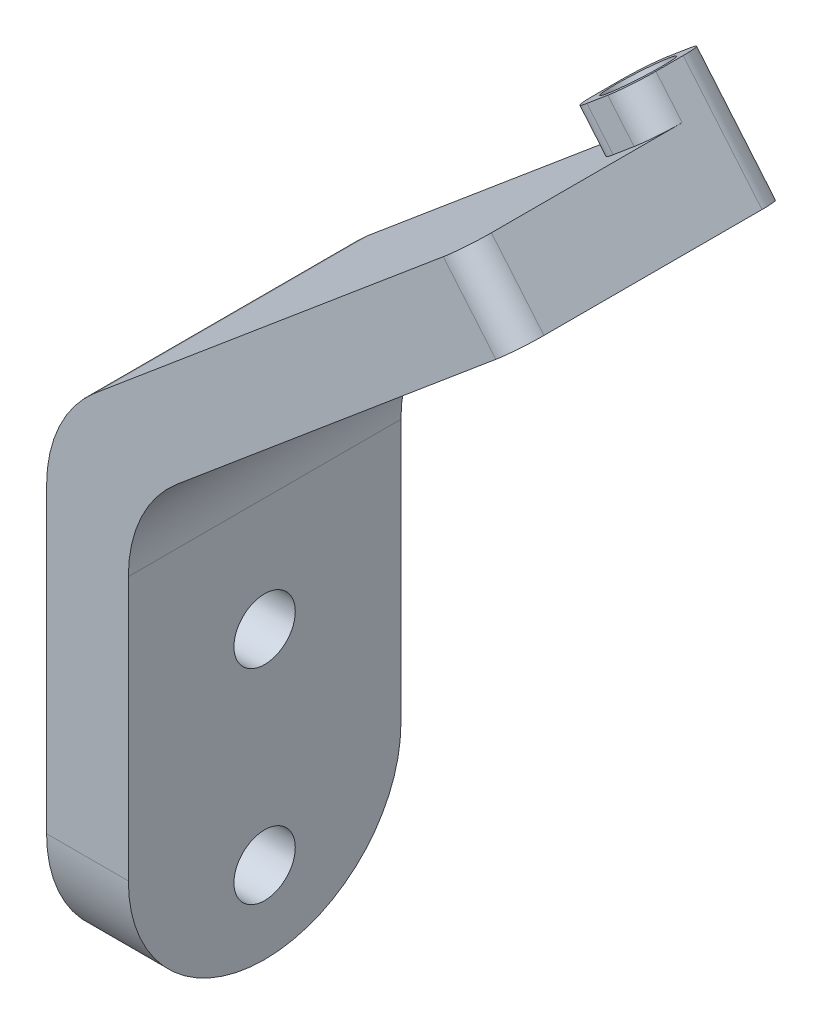
SolidWorks part; units mm, degrees
ref_plane "Plan de face" through (0, 0, 0) normal (0, 0, 1) x (1, 0, 0)
ref_plane "Plan de dessus" through (0, 0, 0) normal (0, 1, 0) x (1, 0, 0)
ref_plane "Plan de droite" through (0, 0, 0) normal (1, 0, 0) x (0, 0, -1)
sketch "Esquisse1" plane through (0, 0, 0) normal (0, 0, 1) x (1, 0, 0)
  line L0 (0, 0) -> (0, 36.7978)
  line L1 (0, 36.7978) -> (30.6418, 62.5094)
  line L2 (30.6418, 62.5094) -> (34.4985, 57.9131)
  line L3 (34.4985, 57.9131) -> (6, 34)
  line L4 (6, 34) -> (6, 0)
  line L5 (6, 0) -> (0, 0)
  dimension "D1" = 34
  dimension "D2" = 130
  dimension "D3" = 40
  dimension "D4" = 6
  dimension "D5" = 6
extrude "Boss.-Extru.1" add sketch "Esquisse1" along normal blind 20
sketch "Esquisse2" plane through (6, 0, 0) normal (1, 0, 0) x (0, 0, -1)
  line L0 (-10, 0) -> (-10, 34) construction
  line L1 (-20, 0) -> (0, 0) construction
  line L2 (-20, 34) -> (0, 34) construction
  circle A0 centre (-10, 6) radius 2.25
  circle A1 centre (-10, 21) radius 2.25
  dimension "D1" = 6
  dimension "D2" = 15
  dimension "D3" = 4.5
extrude "Enlèv. mat.-Extru.1" cut sketch "Esquisse2" against normal through all both and the other way through all
sketch "Esquisse3" plane through (-18.1194, 21.5939, 0) normal (-0.6428, 0.766, 0) x (0.766, 0.6428, 0)
  line L0 (63.6532, 0) -> (23.6532, 0) construction
  line L1 (63.6532, -6) -> (57.6532, -6)
  line L2 (63.6532, -6) -> (63.6532, 0)
  line L3 (63.6532, 0) -> (57.6532, 0)
  line L4 (57.6532, -6) -> (57.6532, 0)
  line L5 (63.6532, -20) -> (63.6532, 0) construction
  dimension "D1" = 6
  dimension "D2" = 6
extrude "Boss.-Extru.2" add sketch "Esquisse3" along normal blind 3
sketch "Esquisse4" plane through (-20.0478, 23.892, 0) normal (-0.6428, 0.766, 0) x (0.766, 0.6428, 0)
  line L0 (60.6532, 0) -> (60.6532, -3) construction
  line L1 (60.6532, -3) -> (63.6532, -3) construction
  line L2 (63.6532, -6) -> (63.6532, 0) construction
  line L3 (63.6532, 0) -> (57.6532, 0) construction
  circle A0 centre (60.6532, -3) radius 2.25
  dimension "D1" = 4.5
  dimension "D2" = 3
  dimension "D3" = 3
extrude "Enlèv. mat.-Extru.2" cut sketch "Esquisse4" against normal blind 5
sketch "Esquisse5" plane through (-16.8338, 20.0618, 0) normal (-0.6428, 0.766, 0) x (0.766, 0.6428, 0)
  circle A0 centre (60.6532, -3) radius 1.75
  dimension "D1" = 3.5
extrude "Enlèv. mat.-Extru.3" cut sketch "Esquisse5" against normal through all both and the other way through all
fillet "Congé1" radius 10 4 edges at (6, 34, 10) (0, 36.7978, 10) (3, 0, 0) (3, 0, 20)
fillet "Congé2" radius 2 5 edges at (31.606, 61.3603, 0) (32.5701, 60.2112, 20) (25.0813, 59.8017, 0) (25.0813, 59.8017, 6) (29.6776, 63.6584, 6)
